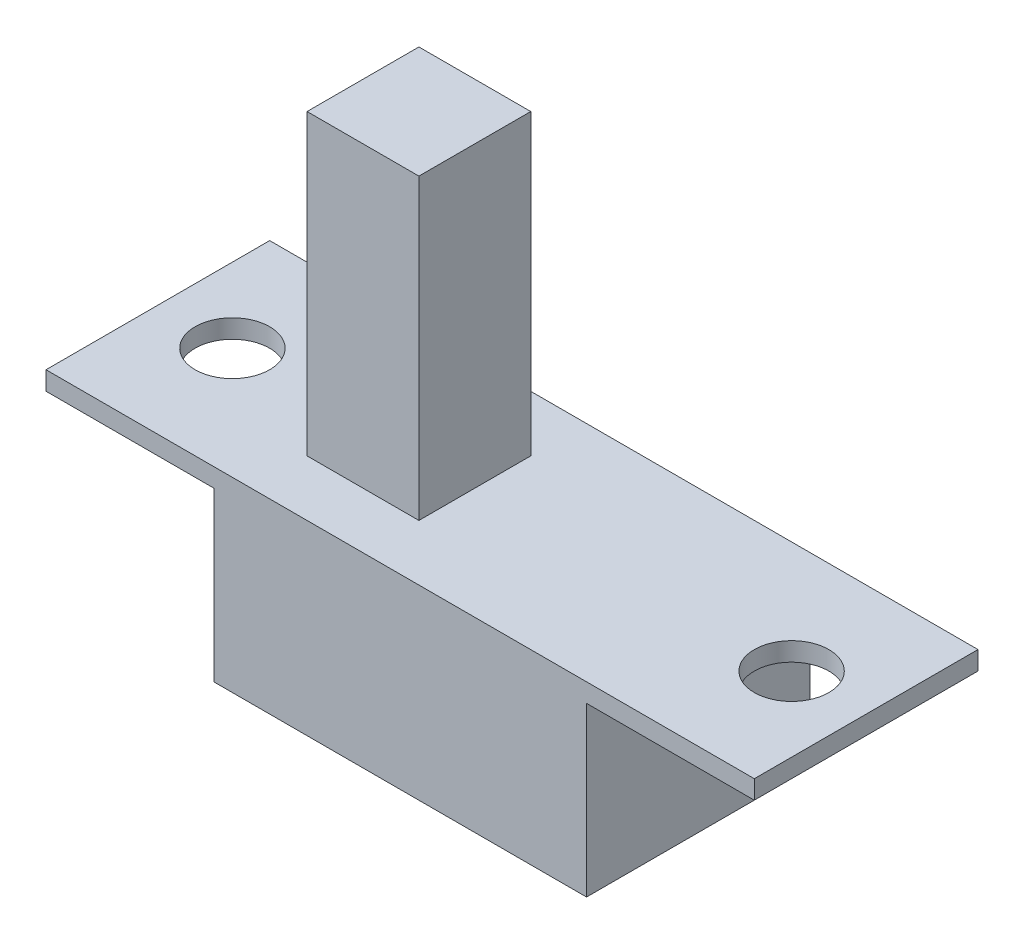
SolidWorks part; units mm, degrees
ref_plane "Front Plane" through (0, 0, 0) normal (0, 0, 1) x (1, 0, 0)
ref_plane "Top Plane" through (0, 0, 0) normal (0, 1, 0) x (1, 0, 0)
ref_plane "Right Plane" through (0, 0, 0) normal (1, 0, 0) x (0, 0, -1)
sketch "Sketch1" plane through (0, 0, 0) normal (0, 1, 0) x (1, 0, 0)
  line L1 (-5, -3) -> (5, -3)
  line L2 (-5, -3) -> (-5, 3)
  line L3 (-5, 3) -> (5, 3)
  line L4 (5, -3) -> (5, 3)
  line L5 (-5, -3) -> (5, 3) construction
  line L6 (-5, 3) -> (5, -3) construction
  point P0 (0, 0)
  dimension "D1" = 10
  dimension "D2" = 6
extrude "Boss-Extrude1" add sketch "Sketch1" along normal blind 5
sketch "Sketch2" plane through (0, 5, 0) normal (0, 1, 0) x (1, 0, 0)
  line L0 (5, 3) -> (-5, 3) construction
  line L1 (-9.5, -3) -> (9.5, -3)
  line L2 (-9.5, -3) -> (-9.5, 3)
  line L3 (-9.5, 3) -> (9.5, 3)
  line L4 (9.5, -3) -> (9.5, 3)
  line L5 (-9.5, -3) -> (9.5, 3) construction
  line L6 (-9.5, 3) -> (9.5, -3) construction
  line L7 (-7.5, 0) -> (-5, 0) construction
  line L8 (-5, 3) -> (-5, -3) construction
  line L9 (-5, 0) -> (5, 0) construction
  line L11 (5, -3) -> (5, 3) construction
  line L13 (5, 0) -> (7.5, 0) construction
  line L14 (7.5, 0) -> (9.5, 0) construction
  line L15 (-7.5, 0) -> (-9.5, 0) construction
  circle A0 centre (-7.5, 0) radius 1
  circle A1 centre (7.5, 0) radius 1
  point P0 (0, 0)
  point P11 (0, 0)
  dimension "D2" = 2
  dimension "D1" = 15
  dimension "D3" = 19
extrude "Boss-Extrude2" add sketch "Sketch2" against normal blind 0.5
sketch "Sketch3" plane through (0, 5, 0) normal (0, 1, 0) x (1, 0, 0)
  line L0 (0, 0) -> (-9.5, 0) construction
  line L1 (-9.5, 3) -> (-9.5, -3) construction
  line L3 (-0.997, -1.5) -> (-3.997, -1.5)
  line L4 (-0.997, -1.5) -> (-0.997, 1.5)
  line L5 (-0.997, 1.5) -> (-3.997, 1.5)
  line L6 (-3.997, -1.5) -> (-3.997, 1.5)
  line L7 (-0.997, -1.5) -> (-3.997, 1.5) construction
  line L8 (-0.997, 1.5) -> (-3.997, -1.5) construction
  line L12 (5, -3) -> (5, 3)
  line L13 (-5, -3) -> (5, -3)
  line L14 (-5, 3) -> (-5, -3)
  line L15 (5, 3) -> (-5, 3)
  line L16 (5, -3) -> (5, 3) construction
  line L17 (-5, -3) -> (5, -3) construction
  line L18 (-5, 3) -> (-5, -3) construction
  line L19 (5, 3) -> (-5, 3) construction
  point P5 (-2.497, 0)
  dimension "D2" = 3
  dimension "D1" = 0
extrude "Boss-Extrude3" add sketch "Sketch3" along normal blind 8
